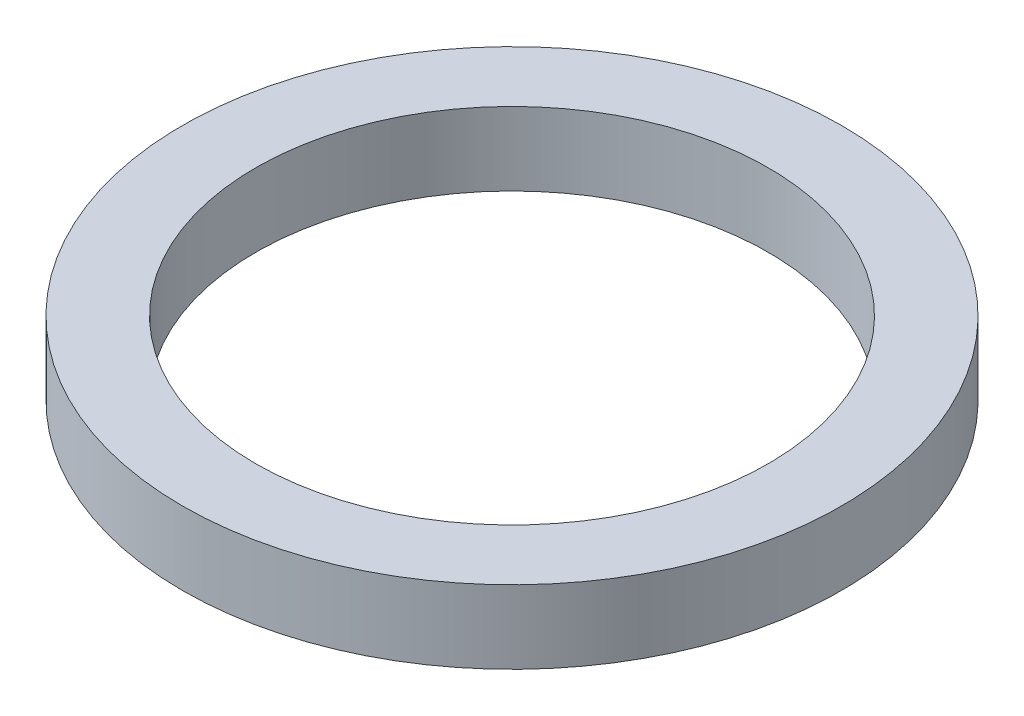
SolidWorks part; units mm, degrees
ref_plane "Front Plane" through (0, 0, 0) normal (0, 0, 1) x (1, 0, 0)
ref_plane "Top Plane" through (0, 0, 0) normal (0, 1, 0) x (1, 0, 0)
ref_plane "Right Plane" through (0, 0, 0) normal (1, 0, 0) x (0, 0, -1)
sketch "Sketch1" plane through (0, 0, 0) normal (0, 1, 0) x (1, 0, 0)
  circle A0 centre (0, 0) radius 35
  circle A1 centre (0, 0) radius 45
  dimension "D1" = 70
  dimension "D2" = 90
extrude "Boss-Extrude1" add sketch "Sketch1" along normal mid plane 10
equation "\"module\" = 0.7"
equation "\"pressure_angle\" = 20.0"
equation "\"h_a\" = 0.7"
equation "\"h_f\" = 0.875"
equation "\"clr_tip_root\" = 0.17500000000000004"
equation "\"bearing_ID\" = 70"
equation "\"bearing_OD\" = 90"
equation "\"bearing_height\" = 10"
equation "\"clearance_planet\" = 1.5"
equation "\"case_dist\" = 6.5"
equation "\"Motor_case_OD_max\" = 131.3"
equation "\"case_mounting_PCD\" = 123.8"
equation "\"bearing mount thickness\" = 8"
equation "\"case_mounting_hole_dia\" = 3"
equation "\"output_mounting_PCD\" = 98"
equation "\"output_mounting_hole_dia\" = 4"
equation "\"clearance_case_mount_holes_shell_thickness\" = 1"
equation "\"motor_case_OD_base\" = 121.8"
equation "\"sec_carrier_thickness\" = 5"
equation "\"sun_coupler_hub_thickness\" = 4"
equation "\"clearance_sun_coupler_sec_carrier\" = 1.5"
equation "\"clearance_motor_and_case\" = 5"
equation "\"motor_OD\" = 106.8"
equation "\"Motor_case_thickness\" = 2.5"
equation "\"Motor_case_ID\" = 116.8"
equation "\"case_mounting_hole_shift\" = 1.0"
equation "\"output_mounting_nut_wrench_size\" = 7"
equation "\"output_mounting_nut_thickness\" = 3.2"
equation "\"case_mounting_hole_allen_socket_dia\" = 5.5"
equation "\"output_mounting_nut_depth\" = 3"
equation "\"case_mounting_bolt_depth\" = 4.5"
equation "\"Ns\" = 48"
equation "\"ring_radial_thickness\" = 5"
equation "\"ring_to_chamfer_clearance\" = 1.5"
equation "\"Motor_case_OD_base_to_chamfer\" = 5"
equation "\"pattern_offset_from_motor_case_OD_base\" = 3"
equation "\"pattern_bulge_dia\" = 3"
equation "\"pattern_num_bulge\" = 18"
equation "\"pattern_depth\" = 2"
equation "\"motor_height\" = 47.6"
equation "\"case_mounting_wrench_size\" = 5.5"
equation "\"case_mounting_nut_clearance\" = 2"
equation "\"base_plate_thickness\" = 4"
equation "\"case_mounting_nut_thickness\" = 2.4"
equation "\"case_mounting_surface_height\" = 4"
equation "\"motor_mount_hole_PCD\" = 40"
equation "\"motor_mount_hole_dia\" = 5"
equation "\"motor_mount_hole_num\" = 4"
equation "\"central_hole_offset_from_motor_mount_PCD\" = 5"
equation "\"wire_slot_dist_from_center\" = 45.5"
equation "\"wire_slot_length\" = 10"
equation "\"wire_slot_radius\" = 3"
equation "\"driver_upper_holes_dist_from_center\" = 29"
equation "\"driver_lower_holes_dist_from_center\" = 13"
equation "\"driver_side_holes_dist_from_center\" = 22.5"
equation "\"driver_mount_holes_dia\" = 3"
equation "\"driver_mount_inserts_OD\" = 4.8"
equation "\"driver_mount_thickness\" = 1.5"
equation "\"driver_mount_height\" = 6"
equation "\"air_flow_hole_offset\" = 3"
equation "\"num_planet\" = 4"
equation "\"planet_pin_bolt_dia\" = 5"
equation "\"planet_pin_socket_head_dia\" = 8.5"
equation "\"carrier_PCD\" = 61.599999999999994"
equation "\"planet_shaft_dia\" = 8"
equation "\"planet_shaft_step_offset\" = 1"
equation "\"carrier_trapezoidal_support_sun_offset\" = 5"
equation "\"carrier_trapezoidal_support_hole_PCD_offset_bearing_ID\" = 4"
equation "\"carrier_trapezoidal_support_hole_dia\" = 3"
equation "\"carrier_trapezoidal_support_hole_socket_head_dia\" = 5.5"
equation "\"carrier_bearing_step_width\" = 1.5"
equation "\"standard_clearance_1_5mm\" = 1.5"
equation "\"standard_fillet_1_5mm\" = 1.5"
equation "\"sun_shaft_bearing_OD\" = 16"
equation "\"sun_shaft_bearing_width\" = 5"
equation "\"standard_bearing_insertion_chamfer\" = 0.5"
equation "\"D1@Sketch1\"=\"bearing_ID\""
equation "\"D2@Sketch1\"=\"bearing_OD\""
equation "\"D1@Boss-Extrude1\"=\"bearing_height\""
equation "\"carrier_trapezoidal_support_hole_wrench_size\" = 5.5"
equation "\"planet_pin_bolt_wrench_size\" = 8"
equation "\"Np_b\" = 40"
equation "\"pressure angle\" = 20.0"
equation "\"h_b\" = 0.875"
equation "\"dp_s\" = 33.599999999999994"
equation "\"db_s\" = 31.57367205840652"
equation "\"fw_s_calc\" = 5.685933367726717"
equation "\"alpha_s\" = 0.8539582918412343"
equation "\"beta_s\" = 2.0420834163175314"
equation "\"dp_p_b\" = 28.0"
equation "\"db_p_b\" = 26.311393382005434"
equation "\"fw_p_s\" = 25.912913082891553"
equation "\"alpha_p_b\" = 0.8539582918412485"
equation "\"beta_p_b\" = 2.792083416317503"
equation "\"planet_bearing_OD\" = 12"
equation "\"planet_bearing_width\" = 3.5"
equation "\"planet_bore\" = 10"
equation "\"motor_output_hole_PCD\" = 23"
equation "\"motor_output_hole_dia\" = 4"
equation "\"motor_output_hole_num\" = 4"
equation "\"sun_shaft_bearing_ID\" = 8"
equation "\"sun_hub_dia\" = 30.0"
equation "\"sun_central_bolt_dia\" = 5"
equation "\"sun_central_bolt_socket_head_dia\" = 8.5"
equation "\"fw_s_used\" = 63.40868620995457"
equation "\"motor_output_hole_CSK_OD\" = 8"
equation "\"motor_output_hole_CSK_head_height\" = 2.0"
equation "\"bearing_retainer_thickness\" = 2"
equation "\"Np_s\" = 28"
equation "\"fw_p_b\" = 29.99577312706301"
equation "\"dp_p_s\" = 19.599999999999998"
equation "\"db_p_s\" = 18.417975367403802"
equation "\"alpha_p_s\" = 0.8539582918412592"
equation "\"beta_p_s\" = 4.7206548448889105"
equation "\"Nr_b\" = 128"
equation "\"dp_r_b\" = 89.6"
equation "\"db_r_b\" = 84.19645882241738"
equation "\"fw_r_b\" = 29.99577312706301"
equation "\"alpha_r_b\" = 0.8539582918412556"
equation "\"beta_r_b\" = 3.114166583682511"
equation "\"ring_OD_b\" = 99.6"
equation "\"Fillet10\"= IIF ( \"ring_OD_b\" > ( \"bearing_OD\" + 2 * \"bearing mount thickness\" ) , \"suppressed\" , \"unsuppressed\" )"
equation "\"Fillet11\"= IIF ( \"ring_OD_b\" < ( \"bearing_OD\" + 2 * \"bearing mount thickness\" ) , \"suppressed\" , \"unsuppressed\" )"
equation "\"Nr_s\" = 116"
equation "\"clr_tip_root_s\" = 0.17500000000000004"
equation "\"dp_r_s\" = 81.19999999999999"
equation "\"db_r_s\" = 76.30304080781575"
equation "\"fw_r_s\" = 24.412913082891553"
equation "\"alpha_r_s\" = 0.8539582918412556"
equation "\"beta_r_s\" = 3.259640721613546"
equation "\"small_ring_case_thickness\" = 4"
equation "\"carrier_thickness\" = 4"
equation "\"small_ring_output_wall_thickness\" = 5"
equation "\"small_ring_output_wall_to_bearing_shaft_attachement_hole_dia\" = 4"
equation "\"small_ring_output_wall_to_bearing_shaft_attachement_hole_depth\" = 6.5"
equation "\"small_ring_output_wall_to_bearing_shaft_attachement_nut_wrench\" = 7"
equation "\"small_ring_output_wall_to_bearing_shaft_attachement_nut_thickness\" = 3.2"
equation "\"small_ring_output_wall_to_bearing_shaft_attachement_hole_pcd\" = 12"
equation "\"small_ring_output_wall_to_bearing_shaft_attachement_hole_num\" = 3"
equation "\"small_ring_output_wall_to_bearing_shaft_attachement_hole_CSK_OD\" = 8"
equation "\"small_ring_output_wall_to_bearing_shaft_attachement_hole_CSK_head_height\" = 2.0"
equation "\"carrier_small_ring_inner_bearing_ID\" = 20"
equation "\"carrier_small_ring_inner_bearing_OD\" = 32"
equation "\"carrier_small_ring_inner_bearing_height\" = 7"
equation "\"carrier_small_ring_inner_bearing_flap\" = 2"
equation "\"gear_casing_big_ring_to_bearing_dist\" = 34.91291308289155"
equation "\"gear_casing_thickness\" = 4"
